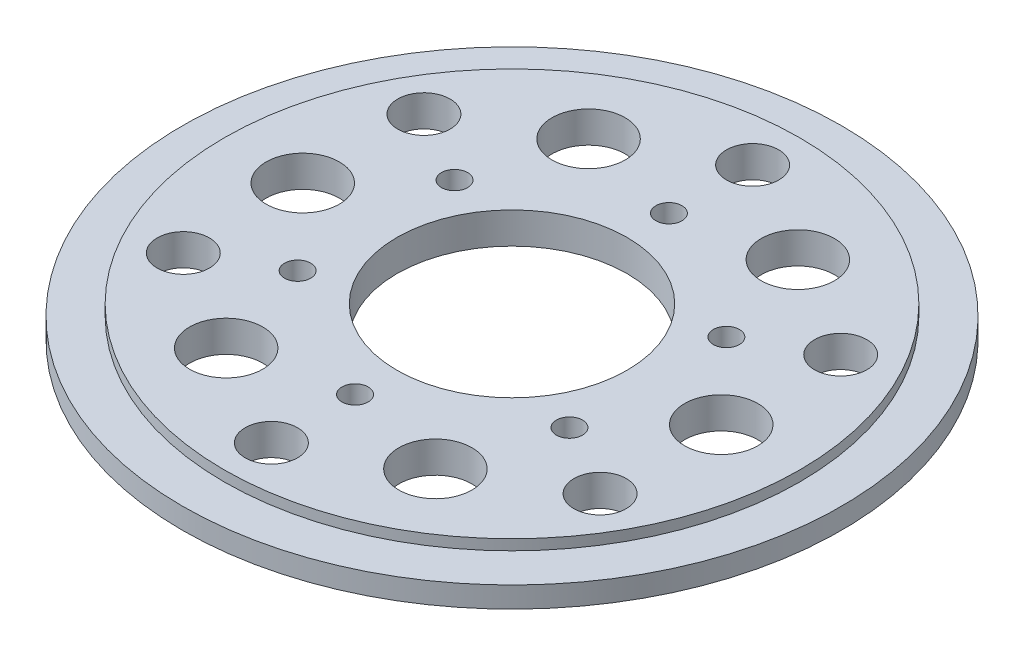
SolidWorks part; units mm, degrees
ref_plane "Front Plane" through (0, 0, 0) normal (0, 0, 1) x (1, 0, 0)
ref_plane "Top Plane" through (0, 0, 0) normal (0, 1, 0) x (1, 0, 0)
ref_plane "Right Plane" through (0, 0, 0) normal (1, 0, 0) x (0, 0, -1)
sketch "Sketch1" plane through (0, 0, 0) normal (0, 1, 0) x (1, 0, 0)
  circle A0 centre (0, 0) radius 27.5
  circle A1 centre (0, 0) radius 11
  circle A2 centre (0, 0) radius 31.5
  dimension "D1" = 55
  dimension "D3" = 22
  dimension "D2" = 4
extrude "Boss-Extrude1" add sketch "Sketch1" along normal blind 3 contours A0 A1 region at (-26.7222, 0, 0)
extrude "Boss-Extrude2" add sketch "Sketch1<3>" along normal blind 2 contours A2 A0 region at (-30.609, 0, 0)
sketch "Sketch1<3>" plane through (0, 0, 0) normal (0, 1, 0) x (1, 0, 0) same geometry as "Sketch1"
hole_wizard "M3x0.5 Tapped Hole1" positions "Sketch2" profile "Sketch4" tap size "M3x0.5" standard "ANSI Metric" end condition through all
sketch "Sketch2" plane through (0, 3, 0) normal (0, 1, 0) x (1, 0, 0)
  line L0 (0, 0) -> (0, 15) construction
  point P0 (0, 15)
  dimension "D1" = 15
sketch "Sketch4" plane through (0, 3, -15) normal (1, 0, 0) x (0, 0, 1)
  line L0 (0, 0) -> (0, 3)
  line L1 (0, 3) -> (1.25, 3)
  line L2 (1.25, 3) -> (1.25, 0)
  line L5 (1.25, 0) -> (0, 0)
  line L11 (0, -6.35) -> (0, 107.95) construction
  dimension "Thru Tap Drill Dia." = 2.5
  dimension "Thru Tap Drill Depth" = 3
sketch "Sketch6" plane through (0, 3, 0) normal (0, 1, 0) x (1, 0, 0)
  line L0 (0, 0) -> (20, 0) construction
  line L1 (0, 0) -> (0, 23) construction
  circle A0 centre (20, 0) radius 3.5
  circle A1 centre (0, 23) radius 2.5
  dimension "D2" = 7
  dimension "D4" = 5
  dimension "D1" = 20
  dimension "D3" = 23
extrude "Cut-Extrude1" cut sketch "Sketch6" against normal through all
pattern_circular "CirPattern1" count 6 over 360 about axis through (0, 3, 0) along (0, -1, 0) of "M3x0.5 Tapped Hole1", "Cut-Extrude1" reverse direction yes
equation "\"Ratio\"= 15"
equation "\"Hull Diameter\"= 3.5in"
equation "\"Fixed Ring Diameter\"= 76"
equation "\"Fixed Pin Diameter\"= 6"
equation "\"Output Ring Diameter\"= 40"
equation "\"Output Pin Diameter\"= 6"
equation "\"Disk Bearing Inner Diameter\"= 9"
equation "\"Disk Bearing Outer Diameter\"= 17"
equation "\"Disk Bearing Height\"= 5"
equation "\"Shaft Bearing Inner Diameter\"= 15"
equation "\"Shaft Bearing Outer Diameter\"= 21"
equation "\"Shaft Bearing Height\"= 4"
equation "\"Eccentricity\"= 1.5"
equation "\"Disk Height\"= 8"
equation "\"Disk Spacing\"= 5"
equation "\"Hull Height\"= 40"
equation "\"Shaft End Bearing Inner Diameter\"= 12"
equation "\"Shaft End Bearing Outer Diameter\"= 18"
equation "\"Shaft End Bearing Height\"= 4"
equation "\"Output Bearing Inner Diameter\"= 55"
equation "\"Output Bearing Outer Diameter\"= 72"
equation "\"Outer Bearing Height\"= 9"
equation "\"D1@Sketch1\"=\"Output Bearing Inner Diameter\""
